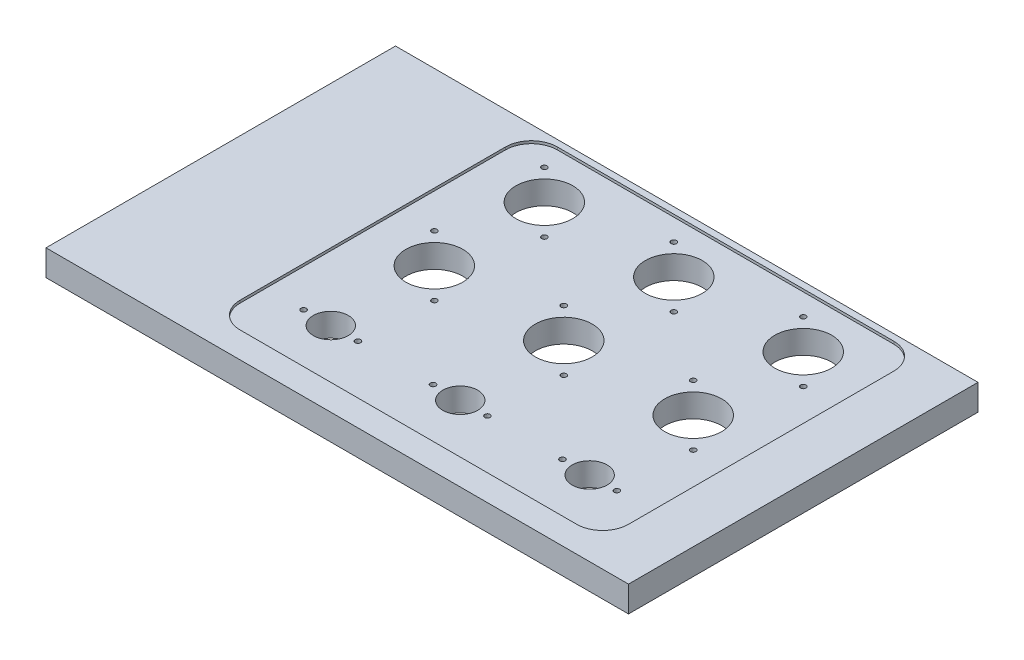
SolidWorks part; units mm, degrees
ref_plane "前视基准面" through (0, 0, 0) normal (0, 0, 1) x (1, 0, 0)
ref_plane "上视基准面" through (0, 0, 0) normal (0, 1, 0) x (1, 0, 0)
ref_plane "右视基准面" through (0, 0, 0) normal (1, 0, 0) x (0, 0, -1)
sketch "草图1" plane through (0, 0, 0) normal (0, 1, 0) x (1, 0, 0)
  line L1 (225, -135) -> (-225, -135)
  line L2 (225, -135) -> (225, 135)
  line L3 (225, 135) -> (-225, 135)
  line L4 (-225, -135) -> (-225, 135)
  line L5 (225, -135) -> (-225, 135) construction
  line L6 (225, 135) -> (-225, -135) construction
  line L7 (-115, 130) -> (185, 130)
  line L8 (-115, 130) -> (-115, -115)
  line L9 (-115, -115) -> (185, -115)
  line L10 (185, 130) -> (185, -115)
  circle A0 centre (-65, 90) radius 22
  circle A1 centre (35, 90) radius 22
  circle A2 centre (135, 90) radius 22
  circle A3 centre (135, 5) radius 22
  circle A4 centre (35, 5) radius 22
  circle A5 centre (-65, 5) radius 22
  circle A6 centre (-65, -75) radius 13.5
  circle A7 centre (35, -75) radius 13.5
  circle A8 centre (135, -75) radius 13.5
  point P0 (0, 0)
  point P28 (0, 0)
  point P29 (0, 0)
  point P30 (0, 0)
  point P31 (0, 0)
  point P32 (0, 0)
  point P33 (0, 0)
  point P34 (0, 0)
  point P35 (0, 0)
  dimension "D7" = 44
  dimension "D8" = 27
  dimension "D1" = 450
  dimension "D2" = 270
  dimension "D3" = 110
  dimension "D4" = 300
  dimension "D5" = 245
  dimension "D6" = 20
  dimension "D9" = 40
  dimension "D10" = 80
  dimension "D11" = 85
  dimension "D12" = 100
  dimension "D13" = 100
  dimension "D14" = 50
extrude "凸台-拉伸1" add sketch "草图1" against normal blind 20 contours L4 L3 L2 L1
extrude "切除-拉伸1" cut sketch "草图1<3>" against normal blind 2 contours L8 L9 L10 L7
sketch "草图1<3>" plane through (0, 0, 0) normal (0, 1, 0) x (1, 0, 0) same geometry as "草图1"
extrude "切除-拉伸2" cut sketch "草图1<4>" against normal up to next contours A0 | A1 | A2 | A3 | A4 | A5 | A6 | A7 | A8 region at (-65, 0, -90) region at (35, 0, -90) region at (135, 0, -90) region at (135, 0, -5) region at (35, 0, -5) region at (-65, 0, -5) region at (-65, 0, 75) region at (35, 0, 75) region at (135, 0, 75)
sketch "草图1<4>" plane through (0, 0, 0) normal (0, 1, 0) x (1, 0, 0) same geometry as "草图1"
fillet "圆角1" radius 20 4 edges at (-115, -1, 115) (185, -1, 115) (185, -1, -130) (-115, -1, -130)
sketch "草图3" plane through (0, -2, 0) normal (0, 1, 0) x (1, 0, 0)
  line L0 (-65, 90) -> (-15.7795, 90) construction
  line L1 (-65, 90) -> (-88.3345, 113.3345) construction
  line L2 (-65, 90) -> (-41.6655, 66.6655) construction
  line L3 (-99.318, -75) -> (174.0386, -75) construction
  line L4 (-65, -75) -> (-65, -47.5705) construction
  line L5 (35, -75) -> (35, -47.5705) construction
  line L6 (135, -75) -> (135, -52.2116) construction
  circle A0 centre (-65, 90) radius 33 construction
  circle A1 centre (35, 90) radius 33 construction
  circle A2 centre (135, 90) radius 33 construction
  circle A3 centre (135, 5) radius 33 construction
  circle A4 centre (35, 5) radius 33 construction
  circle A5 centre (-65, 5) radius 33 construction
  circle A6 centre (-41.6655, 66.6655) radius 2.1
  circle A7 centre (-88.3345, 113.3345) radius 2.1
  circle A8 centre (58.3345, 66.6655) radius 2.1
  circle A9 centre (11.6655, 113.3345) radius 2.1
  circle A10 centre (158.3345, 66.6655) radius 2.1
  circle A11 centre (111.6655, 113.3345) radius 2.1
  circle A12 centre (58.3345, -18.3345) radius 2.1
  circle A13 centre (11.6655, 28.3345) radius 2.1
  circle A14 centre (158.3345, -18.3345) radius 2.1
  circle A15 centre (111.6655, 28.3345) radius 2.1
  circle A16 centre (-41.6655, -18.3345) radius 2.1
  circle A17 centre (-88.3345, 28.3345) radius 2.1
  circle A18 centre (-65, -75) radius 13.5 construction
  circle A19 centre (-65, -75) radius 13.5 construction
  circle A20 centre (-86, -75) radius 2.1
  circle A21 centre (-44, -75) radius 2.1
  circle A22 centre (14, -75) radius 2.1
  circle A23 centre (56, -75) radius 2.1
  circle A24 centre (114, -75) radius 2.1
  circle A25 centre (156, -75) radius 2.1
  point P69 (0, 0)
  point P70 (0, 0)
  dimension "D1" = 66
  dimension "D2" = 4.2
  dimension "D3" = 45
  dimension "D4" = 42
  dimension "D5" = 42
  dimension "D6" = 42
extrude "切除-拉伸3" cut sketch "草图3" against normal blind 10
sketch "草图4" plane through (0, -20, 0) normal (0, -1, 0) x (1, 0, 0)
  line L0 (225, 135) -> (225, -135) construction
  line L1 (225, 135) -> (-225, 135) construction
  circle A0 centre (-124, 65) radius 3.35
  circle A1 centre (210, 65) radius 3.35
  circle A2 centre (210, 30) radius 3.35
  circle A3 centre (210, -70) radius 3.35
  circle A4 centre (-174, -70) radius 3.35
  circle A5 centre (-174, 30) radius 3.35
  circle A6 centre (-124, -105) radius 3.35
  circle A7 centre (100, -105) radius 3.35
  circle A8 centre (100, -5) radius 3.35
  point P22 (0, 0)
  point P23 (0, 0)
  point P24 (0, 0)
  point P25 (0, 0)
  point P26 (0, 0)
  point P27 (0, 0)
  point P28 (0, 0)
  point P29 (0, 0)
  point P30 (0, 0)
  point P31 (0, 0)
  dimension "D9" = 6.7
  dimension "D1" = 15
  dimension "D2" = 110
  dimension "D3" = 224
  dimension "D4" = 50
  dimension "D5" = 170
  dimension "D6" = 100
  dimension "D7" = 70
  dimension "D8" = 70
  dimension "D10" = 35
extrude "切除-拉伸4" cut sketch "草图4" against normal blind 12
